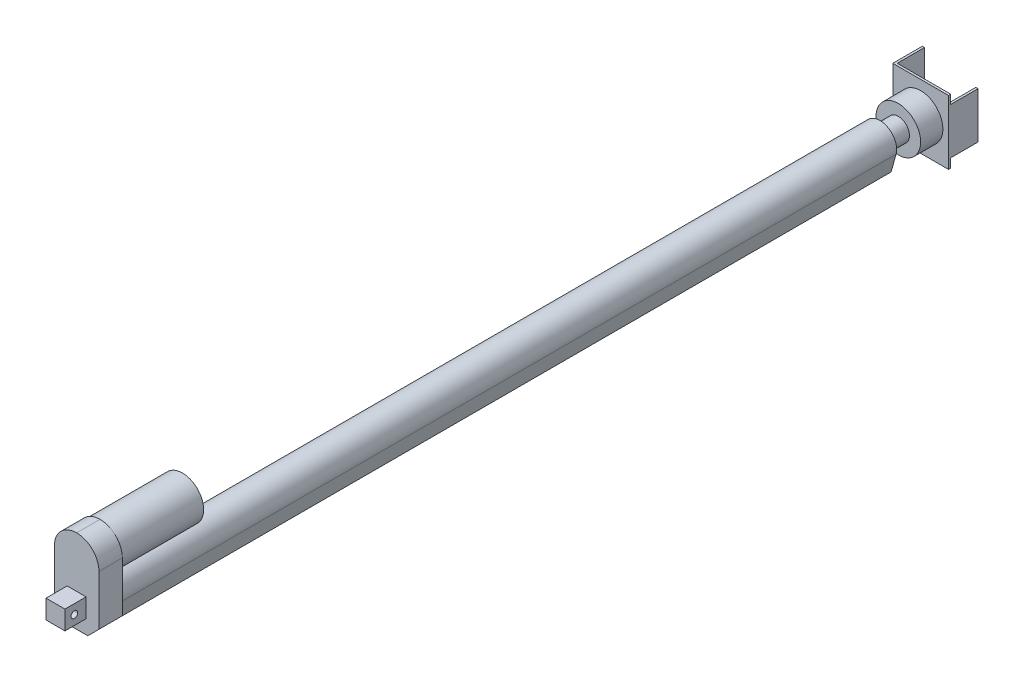
SolidWorks part; units mm, degrees
ref_plane "前视基准面" through (0, 0, 0) normal (0, 0, 1) x (1, 0, 0)
ref_plane "上视基准面" through (0, 0, 0) normal (0, 1, 0) x (1, 0, 0)
ref_plane "右视基准面" through (0, 0, 0) normal (1, 0, 0) x (0, 0, -1)
other "Configuration Table"
sketch "草图1" plane through (0, 0, 0) normal (0, 0, 1) x (1, 0, 0)
  line L1 (-20, 37.5) -> (20, 37.5)
  line L2 (-20, 37.5) -> (-20, -37.5)
  line L3 (-20, -37.5) -> (20, -37.5)
  line L4 (20, 37.5) -> (20, -37.5)
  dimension "D1" = 75
  dimension "D2" = 40
  dimension "D3" = 20
  dimension "D4" = 37.5
extrude "凸台-拉伸1" add sketch "草图1" along normal blind 21
fillet "圆角1" radius 20 2 edges at (-20, 37.5, 10.5) (20, 37.5, 10.5)
chamfer "倒角1" distance 10 angle 45 2 edges at (-20, -37.5, 10.5) (20, -37.5, 10.5)
sketch "草图2" plane through (0, 0, 0) normal (0, 0, -1) x (-1, 0, 0)
  line L0 (10, -37.5) -> (-10, -37.5) construction
  line L1 (-10, -37.5) -> (10, -37.5)
  line L2 (10, -37.5) -> (14.4499, -21.5251)
  line L3 (-10, -37.5) -> (-14.4499, -21.5251)
  arc A0 (14.4499, -21.5251) -> (-14.4499, -21.5251) centre (0, -17.5) ccw
  circle A1 centre (0, -17.5) radius 20 construction
  dimension "D1" = 30
  dimension "D2" = 40
extrude "凸台-拉伸2" add sketch "草图2" along normal blind 700
sketch "草图3" plane through (0, 0, 0) normal (0, 0, -1) x (-1, 0, 0)
  circle A0 centre (0, 17.5) radius 19
  arc A1 (20, 17.5) -> (0, 37.5) centre (0, 17.5) ccw construction
  point P2 (2.3419, 18.8063)
  dimension "D1" = 38
extrude "凸台-拉伸4" add sketch "草图3" along normal blind 74
sketch "草图4" plane through (0, 0, 21) normal (0, 0, 1) x (1, 0, 0)
  line L0 (-10, -37.5) -> (10, -37.5) construction
  line L1 (-8.5, -8) -> (8.5, -8)
  line L2 (-8.5, -8) -> (-8.5, -25)
  line L3 (-8.5, -25) -> (8.5, -25)
  line L4 (8.5, -8) -> (8.5, -25)
  dimension "D1" = 17
  dimension "D2" = 8.5
  dimension "D3" = 12.5
extrude "凸台-拉伸5" add sketch "草图4" along normal blind 19
sketch "草图5" plane through (-8.5, 0, 0) normal (-1, 0, 0) x (0, 0, 1)
  line L0 (40, -8) -> (40, -25) construction
  line L1 (40, -8) -> (21, -8) construction
  circle A0 centre (31.5, -16.5) radius 3
  dimension "D1" = 8.5
  dimension "D2" = 6
  dimension "D3" = 8.5
extrude "切除-拉伸1" cut sketch "草图5" against normal blind 19
sketch "草图6" plane through (0, 0, -700) normal (0, 0, -1) x (-1, 0, 0)
  circle A0 centre (0, -17.5) radius 10
  dimension "D1" = 20
extrude "凸台-拉伸6" add sketch "草图6" along normal blind 16.5
sketch "草图7" plane through (0, 0, -716.5) normal (0, 0, -1) x (-1, 0, 0)
  circle A0 centre (0, -17.5) radius 20
  dimension "D1" = 40
extrude "凸台-拉伸7" add sketch "草图7" along normal blind 20
sketch "草图8" plane through (0, 0, -736.5) normal (0, 0, -1) x (-1, 0, 0)
  line L1 (-25, 11.25) -> (25, 11.25)
  line L2 (-25, 11.25) -> (-25, -46.25)
  line L3 (-25, -46.25) -> (25, -46.25)
  line L4 (25, 11.25) -> (25, -46.25)
  circle A0 centre (0, -17.5) radius 20 construction
  dimension "D4" = 28.75
  dimension "D1" = 57.5
  dimension "D2" = 50
  dimension "D3" = 25
extrude "凸台-拉伸8" add sketch "草图8" along normal blind 2
sketch "草图9" plane through (0, 0, -738.5) normal (0, 0, -1) x (-1, 0, 0)
  line L0 (-25, -46.25) -> (25, -46.25) construction
  line L1 (25, 11.25) -> (23, 11.25)
  line L2 (25, 11.25) -> (25, -46.25)
  line L3 (25, -46.25) -> (23, -46.25)
  line L4 (23, 11.25) -> (23, -46.25)
  dimension "D1" = 2
extrude "凸台-拉伸9" add sketch "草图9" along normal blind 24.5
sketch "草图10" plane through (0, 0, -738.5) normal (0, 0, -1) x (-1, 0, 0)
  line L0 (-25, 11.25) -> (-25, -46.25) construction
  line L1 (-25, 3.25) -> (-23, 3.25)
  line L2 (-25, 3.25) -> (-25, -38.25)
  line L3 (-25, -38.25) -> (-23, -38.25)
  line L4 (-23, 3.25) -> (-23, -38.25)
  line L5 (23, 11.25) -> (-25, 11.25) construction
  dimension "D1" = 41.5
  dimension "D2" = 8
  dimension "D3" = 2
extrude "凸台-拉伸10" add sketch "草图10" along normal blind 24.5
